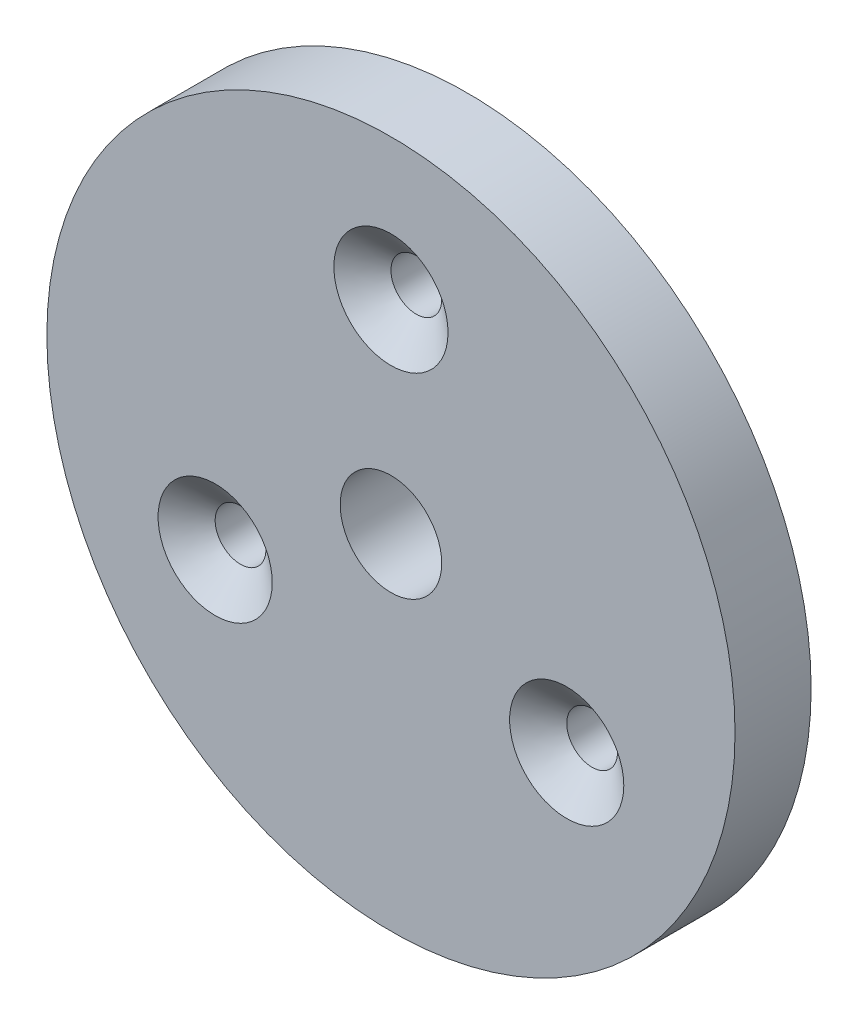
SolidWorks part; units mm, degrees
ref_plane "Front Plane" through (0, 0, 0) normal (1, 0, 0) x (0, 1, 0)
ref_plane "Top Plane" through (0, 0, 0) normal (0, 0, 1) x (0, 1, 0)
ref_plane "Right Plane" through (0, 0, 0) normal (0, 1, 0) x (-1, 0, 0)
sketch "Sketch3" plane through (0, 0, 0) normal (0, 0, 1) x (0, 1, 0)
  circle A0 centre (0, 0) radius 4
  circle A1 centre (0, 0) radius 16 construction
  circle A2 centre (0, 0) radius 27.125
  circle A3 centre (16, 0) radius 2
  circle A4 centre (-8, -13.8564) radius 2
  circle A5 centre (-8, 13.8564) radius 2
  dimension "D1" = 54.25
  dimension "D2" = 8
  dimension "D3" = 32
  dimension "D4" = 4
  dimension "D5" = 3
extrude "Boss-Extrude1" add sketch "Sketch3" along normal blind 6
chamfer "Chamfer1" distance 2.5 distance2 2 3 edges at (-11.8564, -8, 6) (15.8564, -8, 6) (2, 16, 6) first distance on face at (15.8564, -8, 6)
equation "\"SunTeeth\"= 12"
equation "\"PlanetTeeth\" = 20"
equation "\"Module\" = 1"
equation "\"OrbitDiameter\"= \"SunTeeth\" * \"Module\" + \"PlanetTeeth\" * \"Module\""
equation "\"SunBore\"= 8"
equation "\"D1@Sketch3\"= ( \"SunTeeth\" + 2 * \"PlanetTeeth\" ) * \"Module\" + 2.25 * \"Module\""
equation "\"D2@Sketch3\"=\"SunBore\""
equation "\"D3@Sketch3\"=\"OrbitDiameter\""
equation "\"BearingBore\" = 4"
equation "\"D4@Sketch3\"=\"BearingBore\""
equation "\"ScrewCircle\"=31"
equation "\"BearingDiameter\" = 13"
